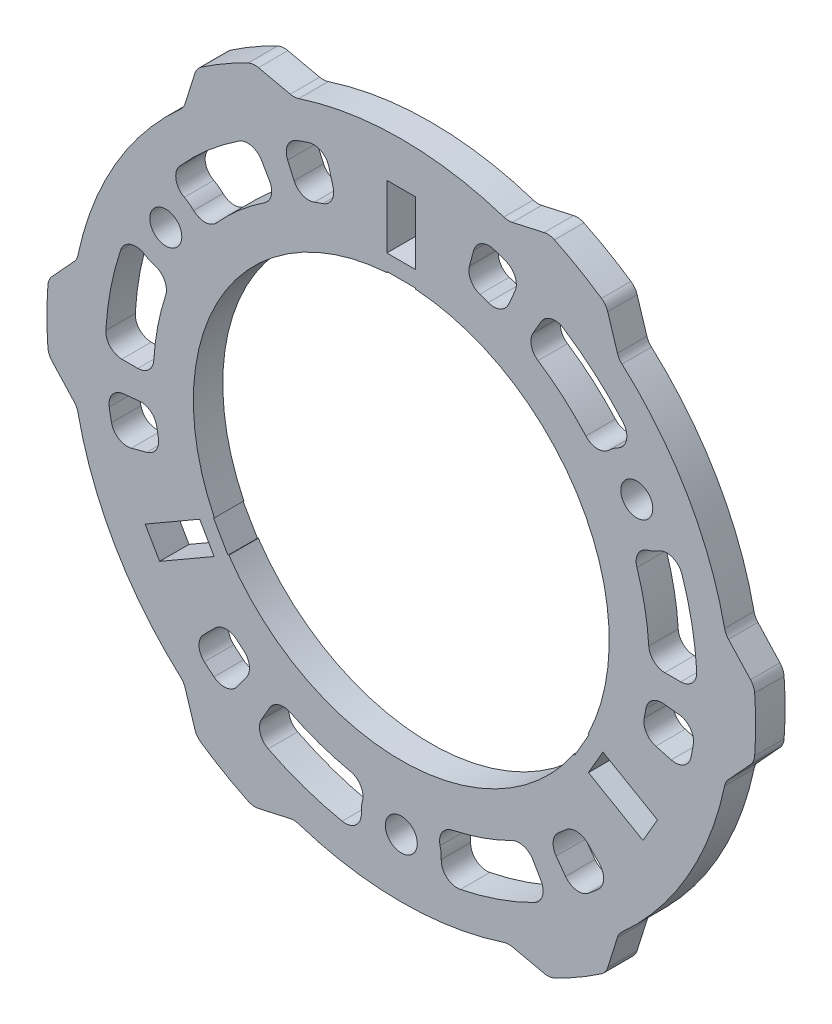
SolidWorks part; units mm, degrees
ref_plane "Front Plane" through (0, 0, 0) normal (0, 0, 1) x (1, 0, 0)
ref_plane "Top Plane" through (0, 0, 0) normal (0, 1, 0) x (1, 0, 0)
ref_plane "Right Plane" through (0, 0, 0) normal (1, 0, 0) x (0, 0, -1)
sketch "Sketch1" plane through (0, 0, 0) normal (0, 0, 1) x (1, 0, 0)
  line L0 (0, 0) -> (0, 50.8) construction
  line L1 (47.9712, -31.0114) -> (50.8422, -26.0386)
  line L2 (2.871, 57.05) -> (-2.871, 57.05)
  line L3 (2.871, 57.05) -> (2.871, 44.55)
  line L4 (2.871, 44.55) -> (-2.871, 44.55)
  line L5 (-2.871, 57.05) -> (-2.871, 44.55)
  line L6 (2.871, 57.05) -> (-2.871, 44.55) construction
  line L7 (2.871, 44.55) -> (-2.871, 57.05) construction
  line L8 (47.9712, -31.0114) -> (37.1459, -24.7614)
  line L9 (37.1459, -24.7614) -> (40.0169, -19.7886)
  line L10 (50.8422, -26.0386) -> (40.0169, -19.7886)
  line L11 (47.9712, -31.0114) -> (40.0169, -19.7886) construction
  line L12 (37.1459, -24.7614) -> (50.8422, -26.0386) construction
  line L13 (-50.8422, -26.0386) -> (-47.9712, -31.0114)
  line L14 (-50.8422, -26.0386) -> (-40.0169, -19.7886)
  line L15 (-40.0169, -19.7886) -> (-37.1459, -24.7614)
  line L16 (-47.9712, -31.0114) -> (-37.1459, -24.7614)
  line L17 (-50.8422, -26.0386) -> (-37.1459, -24.7614) construction
  line L18 (-40.0169, -19.7886) -> (-47.9712, -31.0114) construction
  line L19 (-2.871, 41.375) -> (2.871, 41.375)
  line L20 (-2.871, 41.175) -> (-2.871, 41.375)
  line L21 (2.871, 41.175) -> (2.871, 41.375)
  line L22 (34.2231, -23.0739) -> (34.3963, -23.1739)
  line L23 (37.2673, -18.2011) -> (34.3963, -23.1739)
  line L24 (37.0941, -18.1012) -> (37.2673, -18.2011)
  line L25 (-37.0941, -18.1012) -> (-37.2673, -18.2011)
  line L26 (-34.3963, -23.1739) -> (-37.2673, -18.2011)
  line L27 (0, 0) -> (32.5438, 56.3674) construction
  line L28 (-34.2231, -23.0739) -> (-34.3963, -23.1739)
  arc A0 (-2.871, 41.175) -> (-37.0941, -18.1012) centre (0, 0) ccw
  circle A1 centre (0, 0) radius 65.0875
  circle A2 centre (0, 0) radius 50.8 construction
  arc A3 (37.0941, -18.1012) -> (2.871, 41.175) centre (0, 0) ccw
  arc A4 (-34.2231, -23.0739) -> (34.2231, -23.0739) centre (0, 0) ccw
  point P21 (0, 0)
  point P32 (0, 0)
  point P34 (0, 0)
  dimension "D1" = 82.55
  dimension "D2" = 130.175
  dimension "D8" = 3.175
  dimension "D10" = 101.6
  dimension "D3" = 50.8
  dimension "D4" = 12.5
  dimension "D5" = 5.742
  dimension "D7" = 30
  dimension "D6" = 3
  dimension "D9" = 3
extrude "Boss-Extrude1" add sketch "Sketch1" along normal blind 5.842
sketch "Sketch3" plane through (0, 0, 5.842) normal (0, 0, 1) x (1, 0, 0)
  line L0 (0, 0) -> (0, 65.0875) construction
  line L1 (0, 0) -> (-56.3674, 32.5437) construction
  line L2 (-24.6063, 42.6193) -> (-29.3688, 50.8682)
  line L3 (-49.2125, 0) -> (-58.7375, 0)
  line L4 (-41.2731, 26.803) -> (-49.2614, 31.9907)
  line L5 (-43.8487, 22.342) -> (-52.3355, 26.6663)
  line L6 (43.8487, 22.342) -> (52.3355, 26.6663)
  line L7 (41.2731, 26.803) -> (49.2614, 31.9907)
  line L8 (24.6063, 42.6193) -> (29.3688, 50.8682)
  line L9 (49.2125, 0) -> (58.7375, 0)
  line L10 (-2.5756, -49.1451) -> (-3.0741, -58.657)
  line L11 (2.5756, -49.1451) -> (3.0741, -58.657)
  line L12 (24.6062, -42.6193) -> (29.3687, -50.8682)
  line L13 (-24.6063, -42.6193) -> (-29.3688, -50.8682)
  line L14 (-20.0165, 44.9579) -> (-23.8907, 53.6594)
  line L15 (-15.2024, 56.7361) -> (-12.7371, 47.5356)
  line L16 (-56.7361, -15.2024) -> (-47.5356, -12.7371)
  line L17 (-48.9429, -5.1441) -> (-58.4157, -6.1397)
  line L18 (48.9429, -5.1441) -> (58.4157, -6.1397)
  line L19 (56.7361, -15.2024) -> (47.5356, -12.7371)
  line L20 (15.2024, 56.7361) -> (12.7371, 47.5356)
  line L21 (20.0165, 44.9579) -> (23.8907, 53.6594)
  line L22 (-28.9264, -39.8137) -> (-34.525, -47.5196)
  line L23 (-41.5337, -41.5337) -> (-34.7985, -34.7985)
  line L24 (41.5337, -41.5337) -> (34.7985, -34.7985)
  line L25 (28.9264, -39.8137) -> (34.525, -47.5196)
  circle A0 centre (0, 0) radius 65.0875 construction
  arc A1 (-29.3688, 50.8682) -> (-49.2614, 31.9907) centre (0, 0) ccw
  arc A2 (-24.6063, 42.6193) -> (-41.2731, 26.803) centre (0, 0) ccw
  arc A3 (-43.8487, 22.342) -> (-49.2125, 0) centre (0, 0) ccw
  circle A4 centre (0, 0) radius 49.2125 construction
  circle A5 centre (0, 0) radius 58.7375 construction
  arc A6 (-52.3355, 26.6663) -> (-58.7375, 0) centre (0, 0) ccw
  arc A7 (58.7375, 0) -> (52.3355, 26.6663) centre (0, 0) ccw
  arc A8 (49.2614, 31.9907) -> (29.3688, 50.8682) centre (0, 0) ccw
  arc A9 (41.2731, 26.803) -> (24.6063, 42.6193) centre (0, 0) ccw
  arc A10 (49.2125, 0) -> (43.8487, 22.342) centre (0, 0) ccw
  arc A11 (-29.3688, -50.8682) -> (-3.0741, -58.657) centre (0, 0) ccw
  arc A12 (3.0741, -58.657) -> (29.3687, -50.8682) centre (0, 0) ccw
  arc A13 (2.5756, -49.1451) -> (24.6062, -42.6193) centre (0, 0) ccw
  arc A14 (-24.6063, -42.6193) -> (-2.5756, -49.1451) centre (0, 0) ccw
  arc A15 (-24.6063, 42.6193) -> (-41.2731, 26.803) centre (0, 0) ccw
  arc A16 (-29.3688, 50.8682) -> (-49.2614, 31.9907) centre (0, 0) ccw
  arc A17 (-43.8487, 22.342) -> (-49.2125, 0) centre (0, 0) ccw
  arc A18 (-52.3355, 26.6663) -> (-58.7375, 0) centre (0, 0) ccw
  arc A19 (-24.6063, -42.6193) -> (-2.5756, -49.1451) centre (0, 0) ccw
  arc A20 (-29.3688, -50.8682) -> (-3.0741, -58.657) centre (0, 0) ccw
  arc A21 (2.5756, -49.1451) -> (24.6062, -42.6193) centre (0, 0) ccw
  arc A22 (3.0741, -58.657) -> (29.3687, -50.8682) centre (0, 0) ccw
  arc A23 (58.7375, 0) -> (52.3355, 26.6663) centre (0, 0) ccw
  arc A24 (49.2125, 0) -> (43.8487, 22.342) centre (0, 0) ccw
  arc A25 (41.2731, 26.803) -> (24.6063, 42.6193) centre (0, 0) ccw
  arc A26 (49.2614, 31.9907) -> (29.3688, 50.8682) centre (0, 0) ccw
  arc A27 (-12.7371, 47.5356) -> (-20.0165, 44.9579) centre (0, 0) ccw
  arc A28 (-15.2024, 56.7361) -> (-23.8907, 53.6594) centre (0, 0) ccw
  arc A29 (-56.7361, -15.2024) -> (-58.4157, -6.1397) centre (0, 0) cw
  arc A30 (-47.5356, -12.7371) -> (-48.9429, -5.1441) centre (0, 0) cw
  arc A31 (56.7361, -15.2024) -> (58.4157, -6.1397) centre (0, 0) ccw
  arc A32 (47.5356, -12.7371) -> (48.9429, -5.1441) centre (0, 0) ccw
  arc A33 (15.2024, 56.7361) -> (23.8907, 53.6594) centre (0, 0) cw
  arc A34 (12.7371, 47.5356) -> (20.0165, 44.9579) centre (0, 0) cw
  arc A35 (-41.5337, -41.5337) -> (-34.525, -47.5196) centre (0, 0) ccw
  arc A36 (-34.7985, -34.7985) -> (-28.9264, -39.8137) centre (0, 0) ccw
  arc A37 (41.5337, -41.5337) -> (34.525, -47.5196) centre (0, 0) cw
  arc A38 (34.7985, -34.7985) -> (28.9264, -39.8137) centre (0, 0) cw
  point P8 (56.171, 17.1732)
  point P13 (49.2125, 0)
  point P38 (0, 0)
  point P63 (0, 0)
  dimension "D2" = 117.475
  dimension "D1" = 60
  dimension "D4" = 30
  dimension "D5" = 3
  dimension "D7" = 36
  dimension "D8" = 45
  dimension "D3" = 9.525
  dimension "D6" = 3
  dimension "D9" = 3
extrude "Cut-Extrude2" cut sketch "Sketch3" against normal through all contours A2 L2 A1 L4 | L5 A6 L3 A3 | L16 A30 L17 A29 | L15 A28 L14 A27 | L20 A34 L21 A33 | A9 L7 A8 L8 | A10 L9 A7 L6 | A32 L19 A31 L18 | L24 A38 L25 A37 | A13 L11 A12 L12 | A14 L13 A11 L10 | A36 L23 A35 L22 region at (-36.9066, 38.8915, 5.842) region at (-52.1343, 12.5163, 5.842) region at (52.1343, 12.5163, 5.842) region at (36.9066, 38.8915, 5.842) region at (-15.2277, -51.4078, 5.842) region at (15.2277, -51.4078, 5.842) region at (-18.0454, 50.9587, 5.842) region at (-53.1542, -9.8516, 5.842) region at (53.1542, -9.8516, 5.842) region at (18.0454, 50.9587, 5.842) region at (-35.1088, -41.1071, 5.842) region at (35.1088, -41.1071, 5.842)
fillet "Fillet1" radius 3.175 48 edges at (-52.3355, 26.6663, 2.921) (-58.4157, -6.1397, 2.921) (-43.8487, 22.342, 2.921) (-48.9429, -5.1441, 2.921) (-58.7375, 0, 2.921) (-56.7361, -15.2024, 2.921) (-47.5356, -12.7371, 2.921) (-49.2125, 0, 2.921) (-41.2731, 26.803, 2.921) (-49.2614, 31.9907, 2.921) (-20.0165, 44.9579, 2.921) (-12.7371, 47.5356, 2.921) (-15.2024, 56.7361, 2.921) (-23.8907, 53.6594, 2.921) (-29.3688, 50.8682, 2.921) (-24.6063, 42.6193, 2.921) (41.5337, -41.5337, 2.921) (34.525, -47.5196, 2.921) (34.7985, -34.7985, 2.921) (28.9264, -39.8137, 2.921) (3.0741, -58.657, 2.921) (2.5756, -49.1451, 2.921) (24.6062, -42.6193, 2.921) (29.3687, -50.8682, 2.921) (-3.0741, -58.657, 2.921) (-2.5756, -49.1451, 2.921) (-29.3688, -50.8682, 2.921) (-24.6063, -42.6193, 2.921) (-28.9264, -39.8137, 2.921) (-41.5337, -41.5337, 2.921) (-34.7985, -34.7985, 2.921) (-34.525, -47.5196, 2.921) (48.9429, -5.1441, 2.921) (58.4157, -6.1397, 2.921) (56.7361, -15.2024, 2.921) (47.5356, -12.7371, 2.921) (58.7375, 0, 2.921) (49.2125, 0, 2.921) (52.3355, 26.6663, 2.921) (43.8487, 22.342, 2.921) (49.2614, 31.9907, 2.921) (41.2731, 26.803, 2.921) (29.3688, 50.8682, 2.921) (23.8907, 53.6594, 2.921) (15.2024, 56.7361, 2.921) (24.6063, 42.6193, 2.921) (12.7371, 47.5356, 2.921) (20.0165, 44.9579, 2.921)
sketch "Sketch4" plane through (0, 0, 5.842) normal (0, 0, 1) x (1, 0, 0)
  circle A0 centre (0, 0) radius 65.0875
  circle A1 centre (0, 0) radius 65.5875
  dimension "D1" = 0.5
extrude "Boss-Extrude2" add sketch "Sketch4" against normal up to surface (5.842 mm away) up to face at (-15.0326, -50.7493, 0)
sketch "Sketch5" plane through (0, 0, 5.842) normal (0, 0, 1) x (1, 0, 0)
  line L0 (0, 0) -> (64.6093, 37.3022) construction
  line L1 (0, 0) -> (0, 44.55) construction
  line L2 (-2.871, 44.55) -> (2.871, 44.55) construction
  circle A0 centre (46.7437, 26.9875) radius 3.175
  circle A1 centre (46.7437, 26.9875) radius 7.9375
  circle A2 centre (0, -53.975) radius 7.9375
  circle A3 centre (0, -53.975) radius 3.175
  circle A4 centre (-46.7437, 26.9875) radius 7.9375
  circle A5 centre (-46.7437, 26.9875) radius 3.175
  point P17 (0, 0)
  dimension "D2" = 6.35
  dimension "D4" = 15.875
  dimension "D1" = 60
  dimension "D3" = 53.975
  dimension "D5" = 3
extrude "Boss-Extrude3" add sketch "Sketch5" against normal up to surface (5.842 mm away) up to face at (-15.0326, -50.7493, 0)
sketch "Sketch6" plane through (0, 0, 5.842) normal (0, 0, 1) x (1, 0, 0)
  circle A0 centre (46.7437, 26.9875) radius 3.175
  circle A1 centre (0, -53.975) radius 3.175
  circle A2 centre (-46.7437, 26.9875) radius 3.175
  point P9 (0, 0)
  dimension "D2" = 53.975
  dimension "D1" = 3
extrude "Cut-Extrude3" cut sketch "Sketch6" against normal through all
fillet "Fillet2" radius 3.175 12 edges at (47.2378, 34.9096, 2.921) (39.2699, 29.6606, 2.921) (45.3217, 19.1784, 2.921) (53.8515, 23.4544, 2.921) (-39.2699, 29.6606, 2.921) (-45.3217, 19.1784, 2.921) (-53.8515, 23.4544, 2.921) (-47.2378, 34.9096, 2.921) (6.0519, -48.839, 2.921) (-6.0519, -48.839, 2.921) (-6.6137, -58.364, 2.921) (6.6137, -58.364, 2.921)
sketch "Sketch7" plane through (0, 0, 5.842) normal (0, 0, 1) x (1, 0, 0)
  line L0 (0, 0) -> (0, 68.7625) construction
  line L1 (0, 0) -> (34.3813, 59.5501) construction
  line L2 (29.4048, 63.9099) -> (21.1746, 62.0754)
  line L3 (40.6452, 57.4203) -> (43.1716, 49.3754)
  line L4 (70.05, 6.4897) -> (64.3462, 12.7)
  line L5 (70.05, -6.4897) -> (64.3462, -12.7)
  line L6 (40.6452, -57.4203) -> (43.1716, -49.3754)
  line L7 (29.4048, -63.9099) -> (21.1746, -62.0754)
  line L8 (-29.4048, -63.9099) -> (-21.1746, -62.0754)
  line L9 (-40.6452, -57.4203) -> (-43.1716, -49.3754)
  line L10 (-70.05, -6.4897) -> (-64.3462, -12.7)
  line L11 (-70.05, 6.4897) -> (-64.3462, 12.7)
  line L12 (-40.6452, 57.4203) -> (-43.1716, 49.3754)
  line L13 (-29.4048, 63.9099) -> (-21.1746, 62.0754)
  arc A0 (43.1716, 49.3754) -> (21.1746, 62.0754) centre (0, 0) ccw
  arc A1 (40.6452, 57.4203) -> (29.4048, 63.9099) centre (0, 0) ccw
  circle A2 centre (0, 0) radius 65.5875 construction
  circle A3 centre (0, 0) radius 70.35 construction
  circle A4 centre (0, 0) radius 65.5875 construction
  arc A5 (64.3462, -12.7) -> (64.3462, 12.7) centre (0, 0) ccw
  arc A6 (70.05, -6.4897) -> (70.05, 6.4897) centre (0, 0) ccw
  arc A7 (21.1746, -62.0754) -> (43.1716, -49.3754) centre (0, 0) ccw
  arc A8 (29.4048, -63.9099) -> (40.6452, -57.4203) centre (0, 0) ccw
  arc A9 (-43.1716, -49.3754) -> (-21.1746, -62.0754) centre (0, 0) ccw
  arc A10 (-40.6452, -57.4203) -> (-29.4048, -63.9099) centre (0, 0) ccw
  arc A11 (-64.3462, 12.7) -> (-64.3462, -12.7) centre (0, 0) ccw
  arc A12 (-70.05, 6.4897) -> (-70.05, -6.4897) centre (0, 0) ccw
  arc A13 (-21.1746, 62.0754) -> (-43.1716, 49.3754) centre (0, 0) ccw
  arc A14 (-29.4048, 63.9099) -> (-40.6452, 57.4203) centre (0, 0) ccw
  point P35 (0, 0)
  dimension "D2" = 30
  dimension "D3" = 6
  dimension "D4" = 12.7
  dimension "D1" = 4.7625
extrude "Boss-Extrude4" add sketch "Sketch7" against normal up to surface (5.842 mm away) up to face at (-52.3172, 10.0368, 0)
fillet "Fillet3" radius 3.175 24 edges at (29.4048, 63.9099, 2.921) (40.6452, 57.4203, 2.921) (43.1716, 49.3754, 2.921) (21.1746, 62.0754, 2.921) (64.3462, 12.7, 2.921) (70.05, 6.4897, 2.921) (70.05, -6.4897, 2.921) (64.3462, -12.7, 2.921) (21.1746, -62.0754, 2.921) (29.4048, -63.9099, 2.921) (40.6452, -57.4203, 2.921) (43.1716, -49.3754, 2.921) (-40.6452, -57.4203, 2.921) (-29.4048, -63.9099, 2.921) (-21.1746, -62.0754, 2.921) (-43.1716, -49.3754, 2.921) (-70.05, 6.4897, 2.921) (-70.05, -6.4897, 2.921) (-64.3462, -12.7, 2.921) (-64.3462, 12.7, 2.921) (-21.1746, 62.0754, 2.921) (-43.1716, 49.3754, 2.921) (-40.6452, 57.4203, 2.921) (-29.4048, 63.9099, 2.921)
